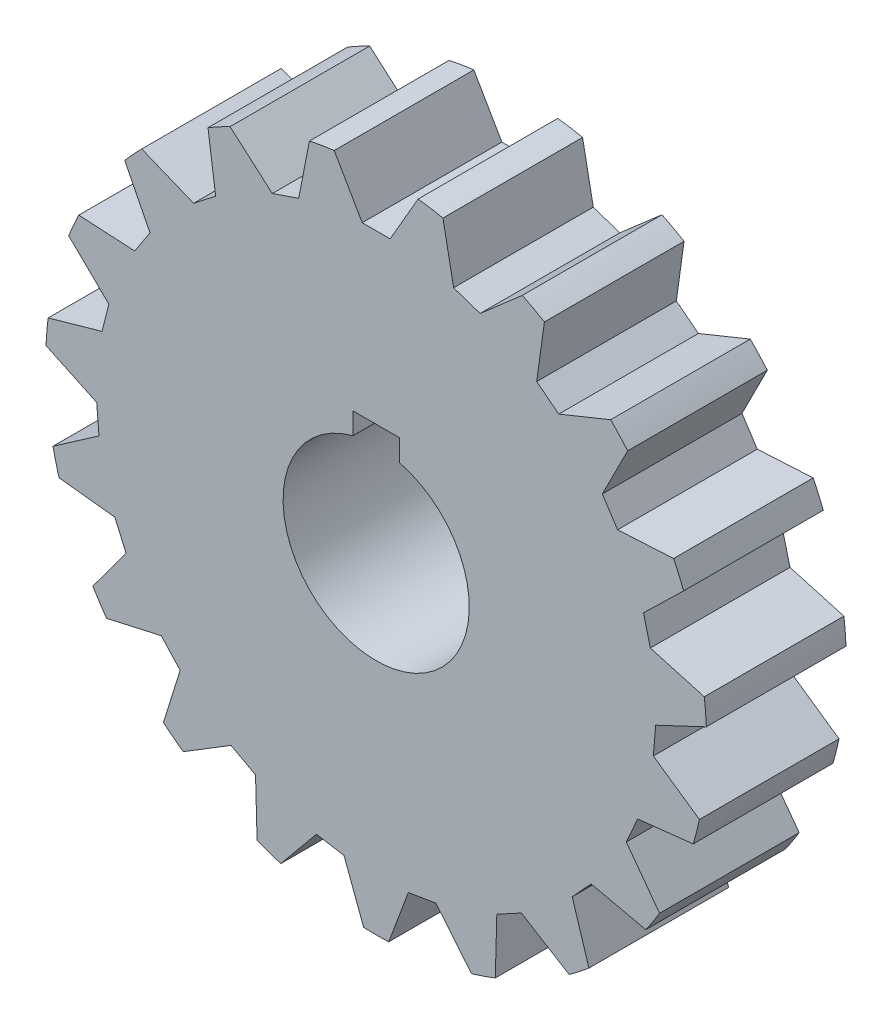
SolidWorks part; units mm, degrees
ref_plane "Front Plane" through (0, 0, 0) normal (0, 0, 1) x (1, 0, 0)
ref_plane "Top Plane" through (0, 0, 0) normal (0, 1, 0) x (1, 0, 0)
ref_plane "Right Plane" through (0, 0, 0) normal (1, 0, 0) x (0, 0, -1)
sketch "Sketch1" plane through (0, 0, 0) normal (0, 0, 1) x (1, 0, 0)
  line L1 (-2.5, 12) -> (2.5, 12)
  line L2 (-2.5, 12) -> (-2.5, 9.6825)
  line L4 (2.5, 12) -> (2.5, 9.6825)
  circle A0 centre (0, 0) radius 35.5
  arc A1 (-2.5, 9.6825) -> (2.5, 9.6825) centre (0, 0) ccw
  point P4 (0, 10)
  dimension "D1" = 71
  dimension "D2" = 20
  dimension "D3" = 5
  dimension "D4" = 12
  dimension "D5" = 2.5
extrude "Boss-Extrude1" add sketch "Sketch1" along normal mid plane 15
sketch "Sketch4" plane through (0, 0, 7.5) normal (0, 0, 1) x (1, 0, 0)
  line L0 (0, 0) -> (0, 30) construction
  line L1 (-1.5, 30) -> (1.5, 30)
  line L2 (1.5, 30) -> (4.5094, 35.2124)
  line L3 (-1.5, 30) -> (-4.5094, 35.2124)
  line L4 (8.3223, 28.8616) -> (7.1684, 34.7687)
  line L5 (11.1597, 27.8875) -> (15.6985, 31.8403)
  line L6 (8.3223, 28.8616) -> (11.1597, 27.8875)
  line L7 (17.2427, 24.5955) -> (18.0694, 30.5573)
  line L8 (19.6101, 22.7529) -> (25.1865, 25.0178)
  line L9 (17.2427, 24.5955) -> (19.6101, 22.7529)
  line L10 (24.2946, 17.6642) -> (27.0123, 23.0345)
  line L11 (25.9354, 15.1527) -> (31.9451, 15.4843)
  line L12 (24.2946, 17.6642) -> (25.9354, 15.1527)
  line L13 (28.7138, 8.8187) -> (33.0279, 13.0156)
  line L14 (29.4502, 5.9105) -> (35.2419, 4.2727)
  line L15 (28.7138, 8.8187) -> (29.4502, 5.9105)
  line L16 (30.0214, -0.9825) -> (35.4645, 1.5862)
  line L17 (29.7737, -3.9723) -> (34.7198, -7.4018)
  line L18 (30.0214, -0.9825) -> (29.7737, -3.9723)
  line L19 (28.0757, -10.6772) -> (34.058, -10.0151)
  line L20 (26.8707, -13.4245) -> (30.4352, -18.2743)
  line L21 (28.0757, -10.6772) -> (26.8707, -13.4245)
  line L22 (23.0876, -19.2149) -> (28.9608, -20.5311)
  line L23 (21.0558, -21.422) -> (22.8525, -27.1664)
  line L24 (23.0876, -19.2149) -> (21.0558, -21.422)
  line L25 (15.5976, -25.6703) -> (20.7252, -28.8222)
  line L26 (12.9592, -27.0981) -> (12.7934, -33.1146)
  line L27 (15.5976, -25.6703) -> (12.9592, -27.0981)
  line L28 (6.4174, -29.3439) -> (10.2437, -33.99)
  line L29 (3.4583, -29.8377) -> (1.3479, -35.4744)
  line L30 (6.4174, -29.3439) -> (3.4583, -29.8377)
  line L31 (-3.4583, -29.8377) -> (-1.3479, -35.4744)
  line L32 (-6.4174, -29.3439) -> (-10.2437, -33.99)
  line L33 (-3.4583, -29.8377) -> (-6.4174, -29.3439)
  line L34 (-12.9592, -27.0981) -> (-12.7934, -33.1146)
  line L35 (-15.5976, -25.6703) -> (-20.7252, -28.8222)
  line L36 (-12.9592, -27.0981) -> (-15.5976, -25.6703)
  line L37 (-21.0558, -21.422) -> (-22.8525, -27.1664)
  line L38 (-23.0876, -19.2149) -> (-28.9608, -20.5311)
  line L39 (-21.0558, -21.422) -> (-23.0876, -19.2149)
  line L40 (-26.8707, -13.4245) -> (-30.4352, -18.2743)
  line L41 (-28.0757, -10.6772) -> (-34.058, -10.0151)
  line L42 (-26.8707, -13.4245) -> (-28.0757, -10.6772)
  line L43 (-29.7737, -3.9723) -> (-34.7198, -7.4018)
  line L44 (-30.0214, -0.9825) -> (-35.4645, 1.5862)
  line L45 (-29.7737, -3.9723) -> (-30.0214, -0.9825)
  line L46 (-29.4502, 5.9105) -> (-35.2419, 4.2727)
  line L47 (-28.7138, 8.8187) -> (-33.0279, 13.0156)
  line L48 (-29.4502, 5.9105) -> (-28.7138, 8.8187)
  line L49 (-25.9354, 15.1527) -> (-31.9451, 15.4843)
  line L50 (-24.2946, 17.6642) -> (-27.0123, 23.0345)
  line L51 (-25.9354, 15.1527) -> (-24.2946, 17.6642)
  line L52 (-19.6101, 22.7529) -> (-25.1865, 25.0178)
  line L53 (-17.2427, 24.5955) -> (-18.0694, 30.5573)
  line L54 (-19.6101, 22.7529) -> (-17.2427, 24.5955)
  line L55 (-11.1597, 27.8875) -> (-15.6985, 31.8403)
  line L56 (-8.3223, 28.8616) -> (-7.1684, 34.7687)
  line L57 (-11.1597, 27.8875) -> (-8.3223, 28.8616)
  circle A0 centre (0, 0) radius 30 construction
  circle A1 centre (0, 0) radius 35.5 construction
  circle A2 centre (0, 0) radius 35.5
  point P7 (0, 30)
  point P85 (0, 0)
  circle M59 centre (0, 0) radius 35.5
  dimension "D1" = 60
  dimension "D2" = 3
  dimension "D3" = 60
  dimension "D4" = 19
extrude "Cut-Extrude2" cut sketch "Sketch4" against normal through all flip side to cut contours L57 L55 L53 L54 L52 L50 L51 L49 L47 L48 L46 L44 L45 L43 L41 L42 L40 L38 L39 L37 L35 L36 L34 L32 L33 L31 L29 L30 L28 L26 L27 L25 L23 L24 L22 L20 L21 L19 M59 region at (0, 0, 7.5)
